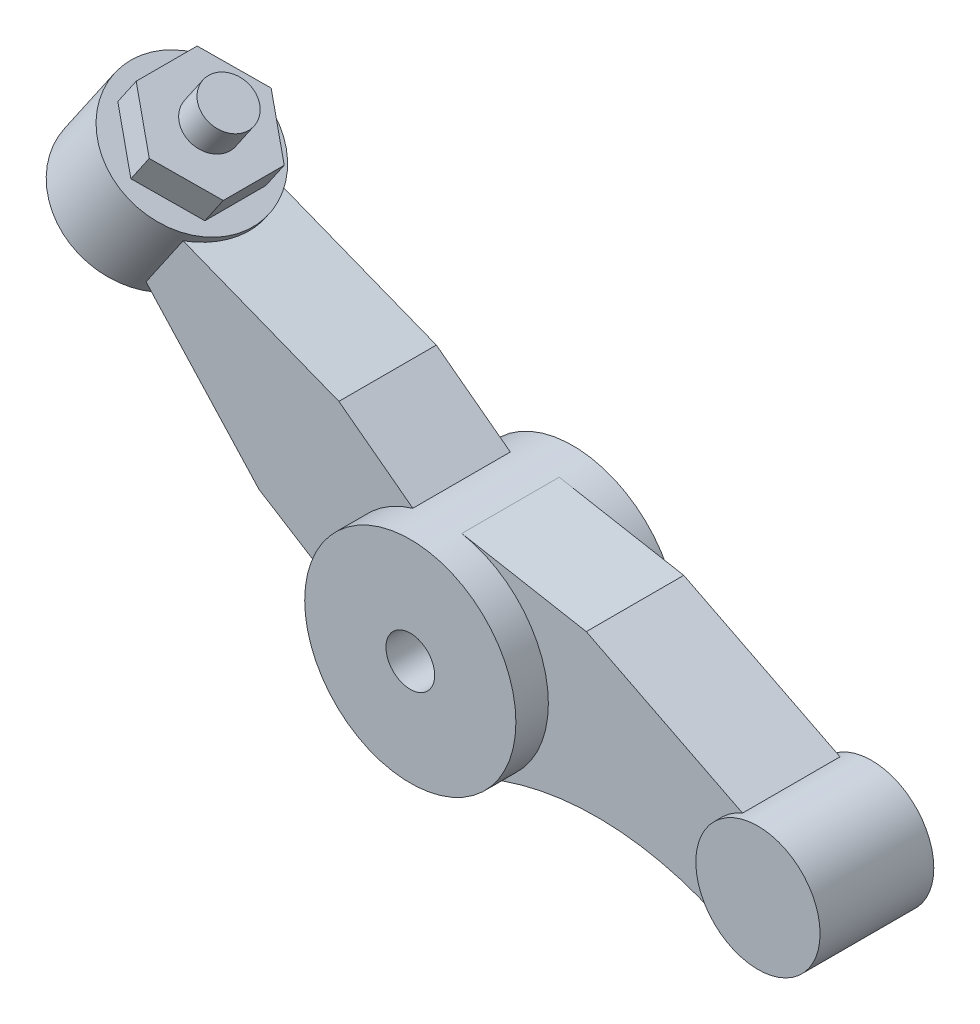
SolidWorks part; units mm, degrees
ref_plane "Front Plane" through (0, 0, 0) normal (0, 0, 1) x (1, 0, 0)
ref_plane "Top Plane" through (0, 0, 0) normal (0, 1, 0) x (1, 0, 0)
ref_plane "Right Plane" through (0, 0, 0) normal (1, 0, 0) x (0, 0, -1)
sketch "Sketch1" plane through (0, 0, 0) normal (0, 0, 1) x (1, 0, 0)
  line L0 (0, 4.285) -> (0, -5.2625) construction
  line L1 (-7.0837, 0) -> (8.8111, 0) construction
  line L2 (0, 0) -> (-3.6604, 2.5129) construction
  line L3 (3.6902, 0.026) -> (1.7667, 0.9992)
  line L4 (1.7667, 0.9992) -> (0.2333, 1.2789)
  line L5 (-3.4694, 2.7912) -> (-3.8515, 2.2347)
  line L6 (-3.4694, 2.7912) -> (-1.2793, 1.9311)
  line L7 (-1.2793, 1.9311) -> (-0.3688, 1.2466)
  line L8 (-2.2618, 0.5) -> (-1.2958, -0.1038)
  line L9 (-3.8515, 2.2347) -> (-2.2618, 0.5)
  circle A0 centre (0, 0) radius 1.3
  circle A1 centre (0, 0) radius 0.3
  circle A2 centre (3.98, -0.682) radius 0.765
  arc A3 (3.5901, -1.3402) -> (0.5106, -1.1955) centre (1.9009, -4.4504) ccw
  point P20 (-1.2793, 1.9311)
  dimension "D1" = 2.6
  dimension "D2" = 0.6
  dimension "D3" = 1.53
  dimension "D4" = 0.682
  dimension "D5" = 3.98
  dimension "D6" = 4.44
  dimension "D7" = 0.675
  dimension "D8" = 0.819
  dimension "D9" = 34.47
extrude "Boss-Extrude1" add sketch "Sketch1" along normal mid plane 2 contours A0 A1 region at (0.9701, 0.8091, 0)
extrude "Boss-Extrude2" add sketch "Sketch1<3>" along normal mid plane 1.4 separate body contours A2 region at (3.98, -0.682, 0)
sketch "Sketch1<3>" plane through (0, 0, 0) normal (0, 0, 1) x (1, 0, 0) same geometry as "Sketch1"
extrude "Boss-Extrude3" add sketch "Sketch1<4>" along normal mid plane 1.2 contours A3 A2 L3 L4 A0 region at (2.1377, -0.0777, 0)
sketch "Sketch1<4>" plane through (0, 0, 0) normal (0, 0, 1) x (1, 0, 0) same geometry as "Sketch1"
extrude "Boss-Extrude4" add sketch "Sketch1<5>" along normal mid plane 1.2 contours A0 L7 L6 L5 L9 L8 region at (-2.1399, 1.4691, 0)
sketch "Sketch1<5>" plane through (0, 0, 0) normal (0, 0, 1) x (1, 0, 0) same geometry as "Sketch1"
sketch "Sketch2" plane through (0, 0, 0) normal (0, 0, 1) x (1, 0, 0)
  line L0 (-3.8515, 2.2347) -> (-3.444, 2.8283)
  line L1 (-3.444, 2.8283) -> (-3.7696, 3.0518)
  line L2 (-3.7696, 3.0518) -> (-4.8331, 1.5026)
  line L3 (-4.2986, 1.8877) -> (-3.8515, 2.2347)
  line L4 (-3.4694, 2.7912) -> (-3.8515, 2.2347) construction
  arc A0 (-4.8331, 1.5026) -> (-4.2986, 1.8877) centre (-4.6351, 1.7912) ccw
  point P8 (0, 0)
  point P11 (-4.2986, 1.8877)
  dimension "D3" = 0.35
  dimension "D1" = 0.72
  dimension "D2" = 0.395
  dimension "D4" = 1
revolve "Revolve1" add sketch "Sketch2" angle 360 about L2
sketch "Sketch4" plane through (0, 0, 0) normal (0, 0, 1) x (1, 0, 0)
  line L7 (-3.6897, 3.1748) -> (-4.3033, 2.281)
  line L8 (-4.3033, 2.281) -> (-5.0535, 2.796)
  line L9 (-5.0535, 2.796) -> (-4.4399, 3.6898)
  line L10 (-4.4399, 3.6898) -> (-3.6897, 3.1748)
  point P4 (-3.7939, 3.023)
  point P5 (-4.202, 2.4285)
  dimension "D1" = 1.0841
  dimension "D2" = 0.91
revolve "Revolve2" add sketch "Sketch4" angle 360 about L7
sketch "Sketch5" plane through (0.2994, 0.4362, 0) normal (0.566, 0.8244, 0) x (0.8244, -0.566, 0)
  line L1 (-4.8387, 0.7506) -> (-5.4887, 0.3753)
  line L2 (-5.4887, 0.3753) -> (-5.4887, -0.3753)
  line L3 (-5.4887, -0.3753) -> (-4.8387, -0.7506)
  line L4 (-4.8387, -0.7506) -> (-4.1887, -0.3753)
  line L5 (-4.1887, -0.3753) -> (-4.1887, 0.3753)
  line L6 (-4.1887, 0.3753) -> (-4.8387, 0.7506)
  circle A0 centre (-4.8387, 0) radius 0.65 construction
  dimension "D1" = 1.3
extrude "Boss-Extrude5" add sketch "Sketch5" along normal blind 0.4
sketch "Sketch6" plane through (0.5258, 0.7659, 0) normal (0.566, 0.8244, 0) x (0.8244, -0.566, 0)
  circle A0 centre (-4.8387, 0) radius 0.3
  dimension "D1" = 0.6
extrude "Boss-Extrude6" add sketch "Sketch6" along normal blind 0.4
